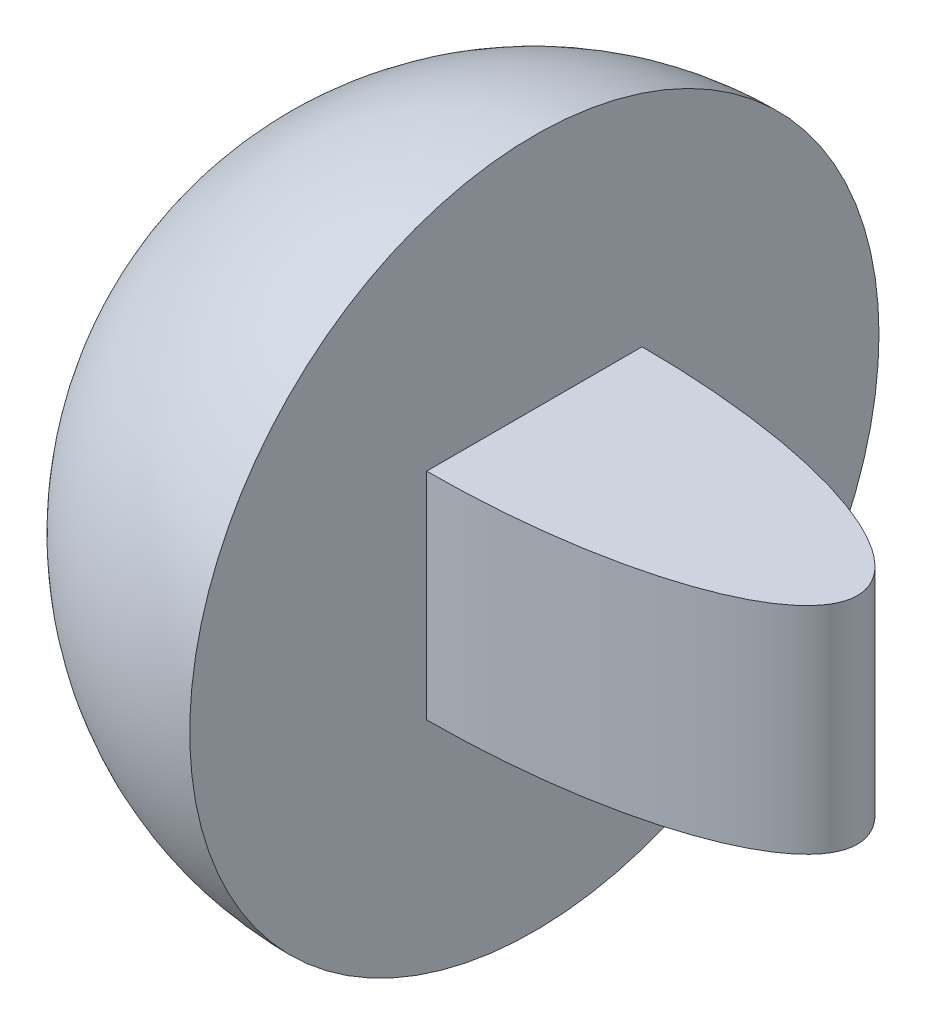
SolidWorks part; units mm, degrees
ref_plane "Alzado" through (0, 0, 0) normal (0, 0, 1) x (1, 0, 0)
ref_plane "Planta" through (0, 0, 0) normal (0, 1, 0) x (1, 0, 0)
ref_plane "Vista lateral" through (0, 0, 0) normal (1, 0, 0) x (0, 0, -1)
sketch "Sketch1" plane through (0, 0, 0) normal (0, 1, 0) x (1, 0, 0)
  line L0 (-75, 0) -> (75, 0) construction
  ellipse E0 centre (0, 0) end of major axis (75, 0) minor radius 25
  dimension "D1" = 50
  dimension "D2" = 150
extrude "Boss-Extrude1" add sketch "Sketch1" along normal blind 25 and the other way blind 25
sketch "Sketch2" plane through (0, 25, 0) normal (0, 1, 0) x (1, 0, 0)
  line L0 (0, 0) -> (75, 0) construction
  ellipse E0 centre (0, 0) end of major axis (75, 0) minor radius 25 construction
  point P9 (50, 0)
  dimension "D1" = 25
ref_axis "Axis1" through (50, 25, 0) along (0, 1, 0)
sketch "Sketch3" plane through (0, 0, 0) normal (0, 1, 0) x (1, 0, 0)
  line L0 (0, 0) -> (-80, 0)
  line L1 (0, 0) -> (0, 80)
  ellipse E0 centre (0, 0) end of major axis (80, 0) minor radius 80 (-80, 0) -> (0, 80) cw
  point P4 (0, 0)
  dimension "D1" = 80
  dimension "D2" = 80
revolve "Revolve1" add sketch "Sketch3" angle 360 about L0
